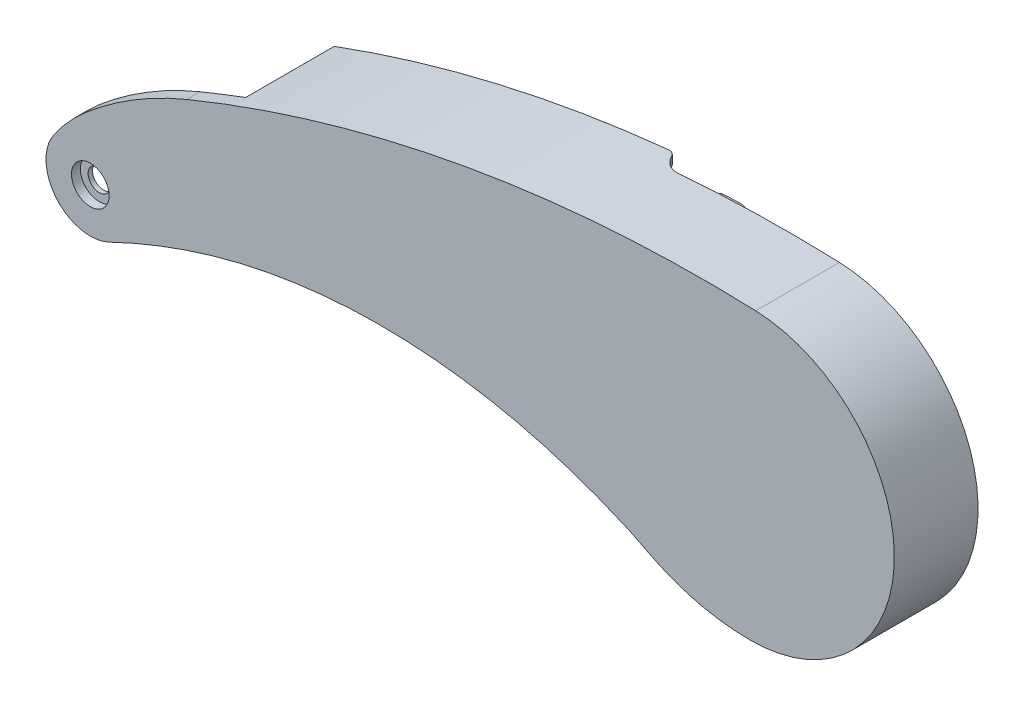
SolidWorks part; units mm, degrees
material "6061-T6 (SS)"
ref_plane "前视基准面" through (0, 0, 0) normal (0, 0, 1) x (1, 0, 0)
ref_plane "上视基准面" through (0, 0, 0) normal (0, 1, 0) x (1, 0, 0)
ref_plane "右视基准面" through (0, 0, 0) normal (1, 0, 0) x (0, 0, -1)
other "Configuration Table"
sketch "草图1" plane through (0, 0, 0) normal (0, 0, 1) x (1, 0, 0)
  line L0 (-74.3846, 0) -> (17.4339, 0) construction
  line L1 (0, 31.8895) -> (0, -25.7876) construction
  line L2 (0, 0) -> (19.2142, 13.9599) construction
  line L3 (0, 0) -> (13.9599, 19.2142) construction
  line L4 (0, 0) -> (-148.9161, -18) construction
  line L6 (0, 0) -> (-1.2281, 22.9672) construction
  line L8 (-1.2281, 22.9672) -> (-150.1441, 4.9672) construction
  line L9 (-150.1441, 4.9672) -> (-148.9161, -18) construction
  line L10 (-148.9161, -18) -> (-97.5528, -158.9319)
  line L12 (0, 0) -> (-103.1063, -167.9797) construction
  circle A117 centre (0, 0) radius 23.75 construction
  circle A118 centre (19.2142, 13.9599) radius 1.6
  circle A119 centre (13.9599, 19.2142) radius 1.6
  circle A120 centre (19.2142, -13.9599) radius 1.6
  circle A121 centre (13.9599, -19.2142) radius 1.6
  circle A122 centre (-13.9599, -19.2142) radius 1.6
  circle A123 centre (-19.2142, -13.9599) radius 1.6
  circle A124 centre (-19.2142, 13.9599) radius 1.6
  circle A125 centre (-13.9599, 19.2142) radius 1.6
  arc A126 (0, -32.5) -> (1.2171, 32.4772) centre (0, 0) ccw
  arc A127 (-157.1671, -12.3502) -> (-144.5702, -27.0063) centre (-148.9161, -18) ccw
  arc A134 (-28.3708, -24.2609) -> (-127.3793, -19.9637) centre (-83.3912, -149.2082) ccw
  arc A135 (-127.3793, -19.9637) -> (-144.5702, -27.0063) centre (-78.0965, -164.7651) ccw
  arc A136 (1.2171, 32.4772) -> (-127.1723, 9.5805) centre (-10.2849, -274.4361) ccw
  arc A138 (-23.6381, -26.5665) -> (-28.3708, -24.2609) centre (-55.9067, -86.7929) ccw
  arc A139 (0, -32.5) -> (-23.6381, -26.5665) centre (0, 17.5518) cw
  circle A153 centre (0, 0) radius 21.8
  arc A155 (-127.1723, 9.5805) -> (-150.1438, -4.5112) centre (-94.9478, -68.7195) ccw
  arc A156 (-150.1438, -4.5112) -> (-157.1671, -12.3502) centre (-123.7132, -35.2574) ccw
  point P27 (0, 0)
  point P73 (0, 0)
  point P83 (0, 0)
  point P105 (0, 0)
  dimension "D3" = 36
  dimension "D4" = 3.2
  dimension "D2" = 47.5
  dimension "D6" = 3.2
  dimension "D8" = 65
  dimension "D15" = 20
  dimension "D16" = 21.8
  dimension "D5" = 18
  dimension "D9" = 18
  dimension "D10" = 150
  dimension "D11" = 23
  dimension "D12" = 150
  dimension "D13" = 103.132
  dimension "D14" = 51.566
  dimension "D7" = 4
extrude "凸台-拉伸1" add sketch "草图1" along normal blind 3 contours A135 A134 A138 A126 A127 A125 A124 A123 A122 A121 A120 A119 A118 region at (-60.0806, 1.6127, 0)
sketch "草图2" plane through (0, 0, 0) normal (0, 0, -1) x (-1, 0, 0)
  line L0 (-28.5, 0) -> (0, 0) construction
  line L2 (0, 0) -> (-20.7479, 9.926) construction
  line L3 (-20.7479, 9.926) -> (128.1682, -8.074) construction
  line L4 (128.1682, -8.074) -> (148.9161, -18) construction
  line L5 (148.9161, -18) -> (265.6411, -112.2087) construction
  line L7 (-13.9568, 11.6234) -> (123.0533, -4.9375) construction
  line L9 (-14.5568, 6.6595) -> (122.4533, -9.9014) construction
  line L11 (19.8643, 25.54) -> (27.8561, 25.1781)
  line L13 (20.7667, -20.0677) -> (28.0595, -16.779)
  line L16 (53.5282, 22.5613) -> (61.4287, 21.3032)
  line L17 (79.2716, 17.6568) -> (87.0322, 15.7143)
  line L19 (80.013, -5.7241) -> (88.0129, -5.7588)
  line L20 (47.3274, -10.2892) -> (55.1237, -8.4956)
  line L21 (0, 0) -> (148.9161, -18) construction
  arc A111 (-1.1422, 30.4786) -> (-30.0624, 5.1483) centre (0, 0) ccw
  arc A112 (0, -30.5) -> (18.2871, -26.8842) centre (0, 17.5518) ccw
  arc A114 (75.0886, -10.9322) -> (61.0732, -12.4928) centre (83.3912, -149.2082) ccw
  arc A116 (144.5702, -27.0063) -> (157.1671, -12.3502) centre (148.9161, -18) ccw
  arc A118 (157.1671, -12.3502) -> (150.1438, -4.5112) centre (123.7132, -35.2574) ccw
  arc A119 (127.1723, 9.5805) -> (-1.2171, 32.4772) centre (10.2849, -274.4361) ccw
  arc A120 (-1.2171, 32.4772) -> (0, -32.5) centre (0, 0) ccw
  arc A121 (-1.0673, 28.48) -> (0, -28.5) centre (0, 0) ccw construction
  arc A122 (0, -32.5) -> (23.6381, -26.5665) centre (0, 17.5518) ccw
  arc A123 (28.3708, -24.2609) -> (23.6381, -26.5665) centre (55.9067, -86.7929) ccw
  arc A124 (127.3793, -19.9637) -> (28.3708, -24.2609) centre (83.3912, -149.2082) ccw
  arc A125 (144.5702, -27.0063) -> (127.3793, -19.9637) centre (78.0965, -164.7651) ccw
  arc A126 (144.5702, -27.0063) -> (157.1671, -12.3502) centre (148.9161, -18) ccw
  arc A128 (127.1723, 9.5805) -> (-1.2171, 32.4772) centre (10.2849, -274.4361) ccw
  arc A129 (-1.2171, 32.4772) -> (0, -32.5) centre (0, 0) ccw
  arc A130 (0, -32.5) -> (23.6381, -26.5665) centre (0, 17.5518) ccw
  arc A131 (28.3708, -24.2609) -> (23.6381, -26.5665) centre (55.9067, -86.7929) ccw
  arc A132 (127.3793, -19.9637) -> (28.3708, -24.2609) centre (83.3912, -149.2082) ccw
  arc A133 (144.5702, -27.0063) -> (127.3793, -19.9637) centre (78.0965, -164.7651) ccw
  arc A134 (0, -28.5) -> (21.749, -23.0407) centre (0, 17.5518) ccw construction
  arc A135 (26.7587, -20.6001) -> (21.749, -23.0407) centre (55.9067, -86.7929) ccw construction
  arc A136 (128.6681, -16.177) -> (26.7587, -20.6001) centre (83.3912, -149.2082) ccw construction
  arc A137 (146.3086, -23.4038) -> (128.6681, -16.177) centre (78.0965, -164.7651) ccw construction
  arc A138 (146.3086, -23.4038) -> (153.7238, -14.4104) centre (148.9161, -18) ccw construction
  arc A139 (153.7238, -14.4104) -> (126.0955, 5.6977) centre (120.8678, -30.5198) ccw construction
  arc A140 (126.0955, 5.6977) -> (-1.0673, 28.48) centre (10.2849, -274.4361) ccw construction
  arc A141 (-28.3421, -2.9958) -> (-28.3421, 2.9958) centre (-28.5, 0) ccw
  arc A142 (-28.3421, 2.9958) -> (-30.0624, 5.1483) centre (-28.2451, 4.837) cw
  arc A143 (-28.3421, -2.9958) -> (-30.0624, -5.1483) centre (-28.2451, -4.837) ccw
  arc A144 (-30.0624, -5.1483) -> (0, -30.5) centre (0, 0) ccw
  circle A145 centre (-28.5, 0) radius 1.6
  arc A146 (-1.1422, 30.4786) -> (0, -30.5) centre (0, 0) ccw construction
  circle A147 centre (-20.7479, 9.926) radius 7 construction
  circle A148 centre (128.1682, -8.074) radius 6 construction
  arc A149 (17.0011, 28.6182) -> (19.8643, 25.54) centre (20, 28.5369) ccw
  arc A150 (27.8561, 25.1781) -> (30.9858, 27.985) centre (27.9918, 28.175) ccw
  arc A151 (17.0011, 28.6182) -> (15.0491, 30.6555) centre (15.0181, 28.672) ccw
  arc A152 (30.9858, 27.985) -> (33.1139, 29.8374) centre (32.9655, 27.8593) cw
  arc A153 (15.0491, 30.6555) -> (-1.1422, 30.4786) centre (10.2849, -274.4361) ccw
  circle A154 centre (20, 28.5369) radius 1.6
  arc A155 (126.6313, 7.6402) -> (-1.1422, 30.4786) centre (10.2849, -274.4361) ccw construction
  arc A156 (19.3156, -24.1418) -> (20.7667, -20.0677) centre (22, -22.8025) cw
  arc A157 (28.0595, -16.779) -> (32.0817, -18.4083) centre (29.2928, -19.5138) cw
  circle A158 centre (22, -22.8025) radius 1.6
  arc A159 (19.3156, -24.1418) -> (18.2871, -26.8842) centre (17.5259, -25.0347) cw
  arc A160 (32.0817, -18.4083) -> (34.6447, -19.5434) centre (33.9409, -17.6713) ccw
  circle A161 centre (54, 25.524) radius 1.6
  arc A162 (27.5648, -22.4305) -> (22.6935, -24.8036) centre (55.9067, -86.7929) ccw construction
  arc A163 (0, -30.5) -> (22.6935, -24.8036) centre (0, 17.5518) ccw construction
  arc A164 (128.0237, -18.0703) -> (27.5648, -22.4305) centre (83.3912, -149.2082) ccw construction
  arc A165 (51.0293, 25.9419) -> (53.5282, 22.5613) centre (54, 25.524) ccw
  arc A166 (61.4287, 21.3032) -> (64.8541, 23.7404) centre (61.9005, 24.2659) ccw
  arc A167 (51.0293, 25.9419) -> (49.3187, 28.1856) centre (49.0649, 26.2183) ccw
  arc A168 (64.8541, 23.7404) -> (67.177, 25.3419) centre (66.8071, 23.393) cw
  arc A169 (49.3187, 28.1856) -> (33.1139, 29.8374) centre (10.2849, -274.4361) ccw
  circle A170 centre (80, 20.567) radius 1.6
  arc A171 (77.077, 21.2425) -> (79.2716, 17.6568) centre (80, 20.567) ccw
  arc A172 (87.0322, 15.7143) -> (90.6571, 17.8435) centre (87.7606, 18.6246) ccw
  arc A173 (77.077, 21.2425) -> (75.5687, 23.6269) centre (75.1443, 21.6892) ccw
  arc A175 (75.5687, 23.6269) -> (67.177, 25.3419) centre (10.2849, -274.4361) ccw
  circle A176 centre (48, -13.2128) radius 1.6
  circle A177 centre (80, -8.7241) radius 1.6
  arc A178 (45.1049, -13.9993) -> (47.3274, -10.2892) centre (48, -13.2128) cw
  arc A180 (45.1049, -13.9993) -> (43.7228, -16.4844) centre (43.1397, -14.5332) cw
  arc A182 (43.7228, -16.4844) -> (34.6447, -19.5434) centre (83.3912, -149.2082) ccw
  arc A183 (77.0018, -8.8285) -> (80.013, -5.7241) centre (80, -8.7241) cw
  arc A184 (88.0129, -5.7588) -> (90.9961, -8.9104) centre (87.9999, -8.7587) cw
  arc A185 (77.0018, -8.8285) -> (75.0886, -10.9322) centre (74.9666, -8.8993) cw
  arc A186 (90.9961, -8.9104) -> (92.8569, -11.0069) centre (92.9935, -9.0116) ccw
  arc A187 (107.3459, -12.77) -> (108.9673, -15.1002) centre (107, -14.7399) cw
  arc A188 (145.4394, -25.205) -> (128.0237, -18.0703) centre (78.0965, -164.7651) ccw construction
  arc A189 (128.0237, -18.0703) -> (27.5648, -22.4305) centre (83.3912, -149.2082) ccw
  arc A190 (145.4394, -25.205) -> (155.4422, -13.3729) centre (148.9161, -18) ccw construction
  arc A191 (75.5687, 23.6269) -> (93.1109, 19.2362) centre (10.2849, -274.4361) cw construction
  arc A192 (90.6571, 17.8435) -> (93.1109, 19.2362) centre (92.5724, 17.327) cw
  arc A193 (155.4422, -13.3729) -> (126.6313, 7.6402) centre (120.8678, -30.5198) ccw construction
  arc A194 (15.0491, 30.6555) -> (33.1139, 29.8374) centre (10.2849, -274.4361) cw construction
  arc A195 (49.3187, 28.1856) -> (67.177, 25.3419) centre (10.2849, -274.4361) cw construction
  arc A196 (93.1109, 19.2362) -> (114.3181, 12.4099) centre (10.2849, -274.4361) cw
  arc A197 (114.3181, 12.4099) -> (116.8779, 13.6021) centre (115, 14.2901) ccw
  arc A198 (55.1237, -8.4956) -> (58.7441, -10.8615) centre (55.7963, -11.4192) cw
  arc A199 (58.7441, -10.8615) -> (61.0732, -12.4928) centre (60.745, -10.4829) ccw
  arc A201 (27.5648, -22.4305) -> (22.6935, -24.8036) centre (55.9067, -86.7929) ccw
  arc A202 (0, -30.5) -> (22.6935, -24.8036) centre (0, 17.5518) ccw
  arc A203 (-1.1422, 30.4786) -> (0, -30.5) centre (0, 0) ccw
  arc A204 (126.4111, 7.731) -> (-1.1422, 30.4786) centre (10.2849, -274.4361) ccw
  arc A205 (148.8401, -6.0279) -> (126.4111, 7.731) centre (94.9478, -68.7195) ccw
  arc A206 (155.5169, -13.4802) -> (148.8401, -6.0279) centre (123.7132, -35.2574) ccw
  arc A207 (157.1671, -12.3502) -> (127.1723, 9.5805) centre (120.8678, -30.5198) ccw construction
  arc A208 (157.1671, -12.3502) -> (150.1438, -4.5112) centre (123.7132, -35.2574) ccw
  arc A209 (150.1438, -4.5112) -> (127.1723, 9.5805) centre (94.9478, -68.7195) ccw
  arc A210 (150.1438, -4.5112) -> (127.1723, 9.5805) centre (94.9478, -68.7195) ccw
  arc A211 (145.4394, -25.205) -> (155.5169, -13.4802) centre (148.9161, -18) ccw
  arc A212 (145.4394, -25.205) -> (128.0237, -18.0703) centre (78.0965, -164.7651) ccw
  point P113 (16.5105, -418.9921)
  arc M20 (127.1723, 9.5805) -> (-1.2171, 32.4772) centre (10.2849, -274.4361) ccw
  arc M21 (-1.2171, 32.4772) -> (0, -32.5) centre (0, 0) ccw
  arc M22 (0, -32.5) -> (23.6381, -26.5665) centre (0, 17.5518) ccw
  arc M23 (23.6381, -26.5665) -> (28.3708, -24.2609) centre (55.9067, -86.7929) cw
  arc M24 (28.3708, -24.2609) -> (127.3793, -19.9637) centre (83.3912, -149.2082) cw
  arc M25 (127.3793, -19.9637) -> (144.5702, -27.0063) centre (78.0965, -164.7651) cw
  dimension "D7" = 150
  dimension "D9" = 14
  dimension "D11" = 12
  dimension "D12" = 150
  dimension "D13" = 8
  dimension "D10" = 2.5
  dimension "D8" = 166.66
  dimension "D14" = 20
  dimension "D15" = 8
  dimension "D16" = 8
  dimension "D17" = 8
  dimension "D18" = 54
  dimension "D19" = 80
  dimension "D20" = 8
  dimension "D21" = 48
  dimension "D22" = 80
  dimension "D23" = 8
  dimension "D6" = 23
  dimension "D25" = 107
  dimension "D26" = 2
  dimension "D27" = 115
  dimension "D28" = 22
  dimension "D4" = 6
  dimension "D5" = 3.2
  dimension "D24" = 2
  dimension "D29" = 2
  dimension "D30" = 2
  dimension "D1" = 0
  dimension "D2" = 2
  dimension "D3" = 2
extrude "凸台-拉伸2" add sketch "草图2" along normal blind 20 contours M20 M21 M22 M23 M24 M25 | A152 A204 A151 A149 L11 A150 A154 | A168 A204 A167 A165 L16 A166 A161 | A192 A204 A173 A171 L17 A172 A170 | A189 A186 A184 L19 A183 A185 A177 | A199 A198 L20 A178 A180 A189 A176 | A159 A202 A201 A189 A160 A157 L13 A156 A158 | A142 A203 A143 A141 A145 region at (-24.5149, 27.9422, 0) region at (-6.9345, 32.3042, 0) region at (-58.4194, 24.4254, 0) region at (29.7748, 3.6145, 0) region at (-84.3067, 19.0872, 0) region at (-25.9289, -20.6304, 0) region at (-52.3362, -11.8146, 0) region at (-84.5374, -8.3524, 0)
sketch "草图4" plane through (0, 0, -20) normal (0, 0, -1) x (-1, 0, 0)
  line L0 (20, 28.5369) -> (27.9918, 28.175) construction
  line L3 (61.9005, 24.2659) -> (54, 25.524) construction
  line L8 (80, 20.567) -> (87.7606, 18.6246) construction
  line L9 (22, -22.8025) -> (29.2928, -19.5138) construction
  line L10 (48, -13.2128) -> (55.7963, -11.4192) construction
  line L11 (80, -8.7241) -> (87.9999, -8.7587) construction
  line L12 (29.2928, -19.5138) -> (25.6464, -21.1581) construction
  line L15 (29.9094, -20.8812) -> (26.263, -22.5255)
  line L24 (28.6761, -18.1464) -> (25.0297, -19.7907)
  line L27 (27.9918, 28.175) -> (23.9959, 28.356) construction
  line L30 (27.924, 26.6766) -> (23.9281, 26.8575)
  line L33 (28.0597, 29.6735) -> (24.0638, 29.8545)
  line L36 (61.9005, 24.2659) -> (57.9502, 24.8949) construction
  line L39 (87.7606, 18.6246) -> (83.8803, 19.5958) construction
  line L40 (87.3964, 17.1695) -> (83.5161, 18.1407)
  line L41 (88.1248, 20.0797) -> (84.2445, 21.0509)
  line L42 (87.9999, -8.7587) -> (84, -8.7414) construction
  line L43 (87.9934, -10.2587) -> (83.9935, -10.2414)
  line L44 (88.0064, -7.2587) -> (84.0065, -7.2414)
  line L45 (55.7963, -11.4192) -> (51.8982, -12.316) construction
  line L46 (56.1326, -12.881) -> (52.2345, -13.7778)
  line L47 (55.46, -9.9574) -> (51.5619, -10.8542)
  line L48 (61.6646, 22.7845) -> (57.7143, 23.4136)
  line L49 (62.1363, 25.7472) -> (58.1861, 26.3763)
  arc A24 (29.9094, -20.8812) -> (28.6761, -18.1464) centre (29.2928, -19.5138) ccw
  arc A25 (25.0297, -19.7907) -> (26.263, -22.5255) centre (25.6464, -21.1581) ccw
  arc A26 (27.924, 26.6766) -> (28.0597, 29.6735) centre (27.9918, 28.175) ccw
  arc A27 (24.0638, 29.8545) -> (23.9281, 26.8575) centre (23.9959, 28.356) ccw
  arc A30 (87.3964, 17.1695) -> (88.1248, 20.0797) centre (87.7606, 18.6246) ccw
  arc A31 (84.2445, 21.0509) -> (83.5161, 18.1407) centre (83.8803, 19.5958) ccw
  arc A32 (87.9934, -10.2587) -> (88.0064, -7.2587) centre (87.9999, -8.7587) ccw
  arc A33 (84.0065, -7.2414) -> (83.9935, -10.2414) centre (84, -8.7414) ccw
  arc A34 (56.1326, -12.881) -> (55.46, -9.9574) centre (55.7963, -11.4192) ccw
  arc A35 (51.5619, -10.8542) -> (52.2345, -13.7778) centre (51.8982, -12.316) ccw
  arc A36 (61.6646, 22.7845) -> (62.1363, 25.7472) centre (61.9005, 24.2659) ccw
  arc A37 (58.1861, 26.3763) -> (57.7143, 23.4136) centre (57.9502, 24.8949) ccw
  point P12 (27.4696, -20.3359)
  point P18 (25.9939, 28.2655)
  point P24 (59.9253, 24.5804)
  point P30 (85.8204, 19.1102)
  point P36 (85.9999, -8.7501)
  point P42 (53.8473, -11.8676)
  dimension "D2" = 1.5
  dimension "D1" = 4
extrude "凸台-拉伸3" add sketch "草图4" along normal blind 3 contours L44 A33 L43 A32 | L33 A27 L30 A26 | L49 A37 L48 A36 | A30 L41 A31 L40 | A34 L47 A35 L46 | A24 L24 A25 L15 region at (-85.9999, -8.7501, -20)
sketch "草图5" plane through (0, 0, -20) normal (0, 0, -1) x (-1, 0, 0)
  circle A0 centre (80, -8.7241) radius 1.6 construction
  circle A2 centre (-28.5, 0) radius 1.6 construction
  circle A4 centre (-28.5, 0) radius 1.6
  circle A6 centre (54, 25.524) radius 1.6 construction
  circle A8 centre (80, 20.567) radius 1.6 construction
  circle A10 centre (80, -8.7241) radius 1.6
  circle A12 centre (48, -13.2128) radius 1.6 construction
  circle A14 centre (22, -22.8025) radius 1.6 construction
  circle A27 centre (20, 28.5369) radius 1.6 construction
  circle A28 centre (54, 25.524) radius 1.6
  circle A29 centre (80, 20.567) radius 1.6
  circle A31 centre (48, -13.2128) radius 1.6
  circle A32 centre (22, -22.8025) radius 1.6
  circle A33 centre (20, 28.5369) radius 1.6
extrude "切除-拉伸1" cut sketch "草图5" against normal up to next
sketch "草图10" plane through (0, 0, 0) normal (0, 0, -1) x (-1, 0, 0)
  circle A0 centre (148.9161, -18) radius 2.5
  dimension "D1" = 5
extrude "切除-拉伸4" cut sketch "草图10" against normal up to next
sketch "草图11" plane through (0, 0, 3) normal (0, 0, 1) x (1, 0, 0)
  circle A0 centre (-148.9161, -18) radius 4.25
  dimension "D1" = 8.5
extrude "切除-拉伸5" cut sketch "草图11" against normal blind 2
sketch "草图13" plane through (0, 0, 3) normal (0, 0, 1) x (1, 0, 0)
  line L0 (-82.9126, 19.8482) -> (-83.8746, 23.7461)
  line L1 (-77.0737, 21.2281) -> (-77.9584, 25.1442)
  line L2 (-56.9642, 25.062) -> (-57.5825, 29.0289)
  line L3 (-51.0272, 25.9272) -> (-51.5669, 29.9056)
  line L4 (-22.9974, 28.4111) -> (-23.1657, 32.4224)
  line L5 (-17.0007, 28.6034) -> (-17.0897, 32.6173)
  line L6 (-83, -8.7157) -> (-83.011, -12.6837)
  line L7 (-77.0031, -8.8605) -> (-77.1835, -12.8243)
  line L10 (-24.5347, -21.1976) -> (-26.898, -24.9303)
  line L11 (-19.2779, -24.0635) -> (-21.0383, -27.8637)
  line L12 (28.5, 3) -> (32.3612, 3)
  line L13 (28.5, -3) -> (32.3612, -3)
  line L14 (28.5, 3) -> (28.5, -3) construction
  line L16 (-45.1135, -14.0301) -> (-46.1946, -17.848)
  line L17 (-50.9188, -12.5194) -> (-51.8359, -16.3799)
  arc A0 (-82.9126, 19.8482) -> (-77.0737, 21.2281) centre (-80, 20.567) ccw
  arc A1 (-56.9642, 25.062) -> (-51.0272, 25.9272) centre (-54, 25.524) ccw
  arc A2 (-22.9974, 28.4111) -> (-17.0007, 28.6034) centre (-20, 28.5369) ccw
  arc A3 (28.5, 3) -> (28.5, -3) centre (28.5, 0) ccw
  arc A5 (-45.1135, -14.0301) -> (-50.9676, -12.7729) centre (-48, -13.2128) ccw
  arc A7 (-23.6381, -26.5665) -> (0, -32.5) centre (0, 17.5518) ccw construction
  arc A8 (1.2171, 32.4772) -> (-127.1723, 9.5805) centre (-10.2849, -274.4361) ccw construction
  arc A9 (-28.3708, -24.2609) -> (-127.3793, -19.9637) centre (-83.3912, -149.2082) ccw construction
  arc A11 (-23.6381, -26.5665) -> (-28.3708, -24.2609) centre (-55.9067, -86.7929) ccw construction
  arc A12 (0, -32.5) -> (1.2171, 32.4772) centre (0, 0) ccw construction
  arc A13 (-17.0897, 32.6173) -> (-23.1657, 32.4224) centre (-10.2849, -274.4361) ccw
  arc A15 (32.3612, -3) -> (32.3612, 3) centre (0, 0) ccw
  arc A16 (-77.1835, -12.8243) -> (-83.011, -12.6837) centre (-83.3912, -149.2082) ccw
  arc A18 (-19.2779, -24.0635) -> (-24.5347, -21.1976) centre (-22, -22.8025) ccw
  arc A19 (-46.1946, -17.848) -> (-51.8359, -16.3799) centre (-83.3912, -149.2082) ccw
  arc A20 (-77.0031, -8.8605) -> (-83, -8.7157) centre (-80, -8.7241) ccw
  arc A21 (-77.9584, 25.1442) -> (-83.8746, 23.7461) centre (-10.2849, -274.4361) ccw
  arc A22 (-51.5669, 29.9056) -> (-57.5825, 29.0289) centre (-10.2849, -274.4361) ccw
  arc A23 (-23.6381, -26.5665) -> (-21.0383, -27.8637) centre (0, 17.5518) ccw
  arc A24 (-23.6381, -26.5665) -> (-26.898, -24.9303) centre (-55.9067, -86.7929) ccw
  circle M9 centre (28.5, 0) radius 1.6
  circle M10 centre (-54, 25.524) radius 1.6
  circle M11 centre (-80, 20.567) radius 1.6
  circle M12 centre (-80, -8.7241) radius 1.6
  circle M13 centre (-48, -13.2128) radius 1.6
  circle M14 centre (-22, -22.8025) radius 1.6
  circle M15 centre (-20, 28.5369) radius 1.6
  arc M17 (-127.3793, -19.9637) -> (-28.3708, -24.2609) centre (-83.3912, -149.2082) cw
  arc M19 (-23.6381, -26.5665) -> (0, -32.5) centre (0, 17.5518) ccw
  arc M20 (0, -32.5) -> (1.2171, 32.4772) centre (0, 0) ccw
  arc M21 (1.2171, 32.4772) -> (-127.1723, 9.5805) centre (-10.2849, -274.4361) ccw
  dimension "D1" = 6
  dimension "D2" = 6
  dimension "D3" = 3
  dimension "D4" = 6
  dimension "D5" = 0
extrude "切除-拉伸6" cut sketch "草图13" against normal blind 2 contours A5 M17 M13 | L11 A18 L10 M19 M14 | L12 L14 L13 M9 M20 | L14 A3 M9 | L4 A2 L5 M21 M15 | L2 A1 L3 M21 M10 | L0 A0 L1 M21 M11 | L7 A20 L6 M17 M12 region at (-22.2972, -27.133, 3) region at (30.7421, 0, 3) region at (-20.1252, 32.441, 3) region at (-54.5626, 29.3843, 3) region at (-83.2943, 21.8217, 3) region at (28.4329, 2.3, 3) region at (-79.9298, -5.8179, 3) region at (-51.2776, -14.4733, 3)
sketch "草图14" plane through (0, 0, 0) normal (0, 0, -1) x (-1, 0, 0)
  circle A0 centre (148.9161, -18) radius 10
  circle A1 centre (148.9161, -18) radius 7
  dimension "D1" = 14
  dimension "D2" = 20
extrude "凸台-拉伸4" add sketch "草图14" along normal blind 1.5
sketch "草图16" plane through (0, 0, 0) normal (0, 0, -1) x (-1, 0, 0)
  line L2 (69.9, 24.8123) -> (66.5383, -11.7121)
  line L3 (72.857, 24.208) -> (69.5822, -11.3731)
  line L4 (41.2273, 29.1197) -> (39.1573, -17.9354) construction
  line L5 (68.061, -11.534) -> (71.3789, 24.5139) construction
  line L6 (39.7324, 29.2684) -> (37.6328, -18.459)
  line L7 (42.7219, 28.9636) -> (40.6809, -17.4318)
  line L8 (103.7768, 16.0167) -> (100.1246, -11.6975) construction
  line L9 (102.3249, 16.48) -> (98.6344, -11.5244)
  line L10 (105.2277, 15.5457) -> (101.6126, -11.8868)
  arc A0 (69.5822, -11.3731) -> (66.5383, -11.7121) centre (83.3912, -149.2082) ccw
  arc A1 (72.857, 24.208) -> (69.9, 24.8123) centre (10.2849, -274.4361) ccw
  arc A2 (43.7228, -16.4844) -> (34.6447, -19.5434) centre (83.3912, -149.2082) ccw construction
  arc A5 (49.3187, 28.1856) -> (33.1139, 29.8374) centre (10.2849, -274.4361) ccw construction
  arc A8 (75.5687, 23.6269) -> (67.177, 25.3419) centre (10.2849, -274.4361) ccw construction
  arc A9 (75.0886, -10.9322) -> (61.0732, -12.4928) centre (83.3912, -149.2082) ccw construction
  arc A10 (75.0886, -10.9322) -> (61.0732, -12.4928) centre (83.3912, -149.2082) ccw construction
  arc A11 (49.3187, 28.1856) -> (33.1139, 29.8374) centre (10.2849, -274.4361) ccw construction
  arc A12 (43.7228, -16.4844) -> (34.6447, -19.5434) centre (83.3912, -149.2082) ccw construction
  arc A13 (40.6809, -17.4318) -> (37.6328, -18.459) centre (83.3912, -149.2082) ccw
  arc A14 (42.7219, 28.9636) -> (39.7324, 29.2684) centre (10.2849, -274.4361) ccw
  arc A15 (114.3181, 12.4099) -> (93.1109, 19.2362) centre (10.2849, -274.4361) ccw construction
  arc A16 (107.3459, -12.77) -> (92.8569, -11.0069) centre (83.3912, -149.2082) ccw construction
  arc A17 (101.6126, -11.8868) -> (98.6344, -11.5244) centre (83.3912, -149.2082) ccw
  arc A18 (105.2277, 15.5457) -> (102.3249, 16.48) centre (10.2849, -274.4361) ccw
  point P33 (71.3789, 24.5139)
  dimension "D3" = 3
  dimension "D1" = 3
  dimension "D2" = 3
extrude "凸台-拉伸5" add sketch "草图16" along normal blind 2
sketch "草图17" plane through (0, 0, 0) normal (0, 0, -1) x (-1, 0, 0)
  line L0 (41.7014, 5.7659) -> (100.4797, 2.4778) construction
  line L1 (40.6809, -17.4318) -> (42.7219, 28.9636) construction
  line L2 (102.3249, 16.48) -> (98.6344, -11.5244) construction
  line L3 (41.7673, 7.2646) -> (100.6762, 3.9692)
  line L4 (102.3249, 16.48) -> (98.6344, -11.5244) construction
  line L5 (41.6355, 4.2673) -> (100.2831, 0.9865)
  line L6 (100.6762, 3.9692) -> (100.2831, 0.9865)
  line L7 (41.6355, 4.2673) -> (41.7673, 7.2646)
  dimension "D1" = 3
extrude "凸台-拉伸6" add sketch "草图17" along normal blind 2
fillet "圆角1" radius 2 14 edges at (-83.8746, 23.7461, 2) (-77.9584, 25.1442, 2) (-57.5825, 29.0289, 2) (-51.5669, 29.9056, 2) (-77.1835, -12.8243, 2) (-83.011, -12.6837, 2) (-21.0383, -27.8637, 2) (32.3612, 3, 2) (32.3612, -3, 2) (-23.1657, 32.4224, 2) (-17.0897, 32.6173, 2) (-46.1946, -17.848, 2) (-51.8359, -16.3799, 2) (-26.898, -24.9303, 2)
sketch "草图20" plane through (0, 0, 3) normal (0, 0, 1) x (1, 0, 0)
  line L0 (30.0874, 3) -> (28.5, 3) construction
  line L1 (28.5, -3) -> (30.0874, -3) construction
  line L2 (-20.1802, -26.0112) -> (-19.2779, -24.0635) construction
  line L3 (-24.5347, -21.1976) -> (-25.967, -23.4599) construction
  line L4 (-45.6536, -15.9376) -> (-45.1135, -14.0301) construction
  line L5 (-50.9188, -12.5194) -> (-51.377, -14.4481) construction
  line L6 (-77.0932, -10.8408) -> (-77.0031, -8.8605) construction
  line L7 (-83, -8.7157) -> (-83.0055, -10.6981) construction
  line L8 (-23.0816, 30.4176) -> (-22.9974, 28.4111) construction
  line L9 (-17.0007, 28.6034) -> (-17.0452, 30.6112) construction
  line L10 (-57.2735, 27.0463) -> (-56.9642, 25.062) construction
  line L11 (-51.0272, 25.9272) -> (-51.2972, 27.9173) construction
  line L12 (-83.3938, 21.798) -> (-82.9126, 19.8482) construction
  line L13 (-77.0737, 21.2281) -> (-77.5162, 23.187) construction
  line L14 (30.0874, 3) -> (28.5, 3)
  line L15 (28.5, -3) -> (30.0874, -3)
  line L16 (-20.1802, -26.0112) -> (-19.2779, -24.0635)
  line L17 (-24.5347, -21.1976) -> (-25.967, -23.4599)
  line L18 (-45.6536, -15.9376) -> (-45.1135, -14.0301)
  line L19 (-50.9188, -12.5194) -> (-51.377, -14.4481)
  line L20 (-77.0932, -10.8408) -> (-77.0031, -8.8605)
  line L21 (-83, -8.7157) -> (-83.0055, -10.6981)
  line L22 (-23.0816, 30.4176) -> (-22.9974, 28.4111)
  line L23 (-17.0007, 28.6034) -> (-17.0452, 30.6112)
  line L24 (-57.2735, 27.0463) -> (-56.9642, 25.062)
  line L25 (-51.0272, 25.9272) -> (-51.2972, 27.9173)
  line L26 (-83.3938, 21.798) -> (-82.9126, 19.8482)
  line L27 (-77.0737, 21.2281) -> (-77.5162, 23.187)
  arc A0 (28.5, 3) -> (28.5, -3) centre (28.5, 0) ccw construction
  arc A1 (32.0603, -5.3279) -> (30.0874, -3) centre (30.0874, -5) ccw construction
  arc A2 (32.0603, -5.3279) -> (32.0603, 5.3279) centre (0, 0) ccw construction
  arc A3 (30.0874, 3) -> (32.0603, 5.3279) centre (30.0874, 5) ccw construction
  arc A4 (-19.2779, -24.0635) -> (-24.5347, -21.1976) centre (-22, -22.8025) ccw construction
  arc A5 (-28.4615, -24.221) -> (-25.967, -23.4599) centre (-27.6568, -22.39) ccw construction
  arc A7 (-23.6381, -26.5665) -> (-19.1298, -28.7) centre (0, 17.5518) ccw construction
  arc A8 (-20.1802, -26.0112) -> (-19.1298, -28.7) centre (-18.3654, -26.8519) ccw construction
  arc A9 (-45.1135, -14.0301) -> (-50.9188, -12.5194) centre (-48, -13.2128) ccw construction
  arc A10 (-53.7569, -15.9382) -> (-51.377, -14.4481) centre (-53.3228, -13.9859) ccw construction
  arc A11 (-44.3019, -18.3987) -> (-53.7569, -15.9382) centre (-83.3912, -149.2082) ccw construction
  arc A12 (-45.6536, -15.9376) -> (-44.3019, -18.3987) centre (-43.7293, -16.4825) ccw construction
  arc A13 (-77.0031, -8.8605) -> (-83, -8.7157) centre (-80, -8.7241) ccw construction
  arc A14 (-84.9822, -12.6924) -> (-83.0055, -10.6981) centre (-85.0055, -10.6925) ccw construction
  arc A15 (-75.2151, -12.9282) -> (-84.9822, -12.6924) centre (-83.3912, -149.2082) ccw construction
  arc A16 (-77.0932, -10.8408) -> (-75.2151, -12.9282) centre (-75.0953, -10.9318) ccw construction
  arc A17 (-22.9974, 28.4111) -> (-17.0007, 28.6034) centre (-20, 28.5369) ccw construction
  arc A18 (-15.0769, 32.6553) -> (-17.0452, 30.6112) centre (-15.0457, 30.6555) ccw construction
  arc A19 (-15.0769, 32.6553) -> (-25.1768, 32.3314) centre (-10.2849, -274.4361) ccw construction
  arc A20 (-23.0816, 30.4176) -> (-25.1768, 32.3314) centre (-25.0798, 30.3338) ccw construction
  arc A21 (-56.9642, 25.062) -> (-51.0272, 25.9272) centre (-54, 25.524) ccw construction
  arc A22 (-49.5711, 30.1696) -> (-51.2972, 27.9173) centre (-49.3153, 28.1861) ccw construction
  arc A23 (-49.5711, 30.1696) -> (-59.5706, 28.7124) centre (-10.2849, -274.4361) ccw construction
  arc A24 (-57.2735, 27.0463) -> (-59.5706, 28.7124) centre (-59.2496, 26.7383) ccw construction
  arc A25 (-82.9126, 19.8482) -> (-77.0737, 21.2281) centre (-80, 20.567) ccw construction
  arc A26 (-75.9933, 25.5814) -> (-77.5162, 23.187) centre (-75.5654, 23.6277) ccw construction
  arc A27 (-75.9933, 25.5814) -> (-85.8275, 23.2574) centre (-10.2849, -274.4361) ccw construction
  arc A28 (-83.3938, 21.798) -> (-85.8275, 23.2574) centre (-85.3355, 21.3188) ccw construction
  arc A29 (28.5, 3) -> (28.5, -3) centre (28.5, 0) ccw
  arc A30 (32.0603, -5.3279) -> (30.0874, -3) centre (30.0874, -5) ccw
  arc A31 (32.0603, -5.3279) -> (32.0603, 5.3279) centre (0, 0) ccw
  arc A32 (30.0874, 3) -> (32.0603, 5.3279) centre (30.0874, 5) ccw
  arc A33 (-19.2779, -24.0635) -> (-24.5347, -21.1976) centre (-22, -22.8025) ccw
  arc A34 (-28.4615, -24.221) -> (-25.967, -23.4599) centre (-27.6568, -22.39) ccw
  arc A35 (-23.6381, -26.5665) -> (-28.4615, -24.221) centre (-55.9071, -86.7927) ccw
  arc A36 (-23.6381, -26.5665) -> (-19.1298, -28.7) centre (0, 17.5518) ccw
  arc A37 (-20.1802, -26.0112) -> (-19.1298, -28.7) centre (-18.3654, -26.8519) ccw
  arc A38 (-45.1135, -14.0301) -> (-50.9188, -12.5194) centre (-48, -13.2128) ccw
  arc A39 (-53.7569, -15.9382) -> (-51.377, -14.4481) centre (-53.3228, -13.9859) ccw
  arc A40 (-44.3019, -18.3987) -> (-53.7569, -15.9382) centre (-83.3912, -149.2082) ccw
  arc A41 (-45.6536, -15.9376) -> (-44.3019, -18.3987) centre (-43.7293, -16.4825) ccw
  arc A42 (-77.0031, -8.8605) -> (-83, -8.7157) centre (-80, -8.7241) ccw
  arc A43 (-84.9822, -12.6924) -> (-83.0055, -10.6981) centre (-85.0055, -10.6925) ccw
  arc A44 (-75.2151, -12.9282) -> (-84.9822, -12.6924) centre (-83.3912, -149.2082) ccw
  arc A45 (-77.0932, -10.8408) -> (-75.2151, -12.9282) centre (-75.0953, -10.9318) ccw
  arc A46 (-22.9974, 28.4111) -> (-17.0007, 28.6034) centre (-20, 28.5369) ccw
  arc A47 (-15.0769, 32.6553) -> (-17.0452, 30.6112) centre (-15.0457, 30.6555) ccw
  arc A48 (-15.0769, 32.6553) -> (-25.1768, 32.3314) centre (-10.2849, -274.4361) ccw
  arc A49 (-23.0816, 30.4176) -> (-25.1768, 32.3314) centre (-25.0798, 30.3338) ccw
  arc A50 (-56.9642, 25.062) -> (-51.0272, 25.9272) centre (-54, 25.524) ccw
  arc A51 (-49.5711, 30.1696) -> (-51.2972, 27.9173) centre (-49.3153, 28.1861) ccw
  arc A52 (-49.5711, 30.1696) -> (-59.5706, 28.7124) centre (-10.2849, -274.4361) ccw
  arc A53 (-57.2735, 27.0463) -> (-59.5706, 28.7124) centre (-59.2496, 26.7383) ccw
  arc A54 (-82.9126, 19.8482) -> (-77.0737, 21.2281) centre (-80, 20.567) ccw
  arc A55 (-75.9933, 25.5814) -> (-77.5162, 23.187) centre (-75.5654, 23.6277) ccw
  arc A56 (-75.9933, 25.5814) -> (-85.8275, 23.2574) centre (-10.2849, -274.4361) ccw
  arc A57 (-83.3938, 21.798) -> (-85.8275, 23.2574) centre (-85.3355, 21.3188) ccw
  circle A58 centre (-19.2142, -13.9599) radius 1.6 construction
  circle A59 centre (-13.9599, -19.2142) radius 1.6 construction
  circle A60 centre (13.9599, -19.2142) radius 1.6 construction
  circle A61 centre (19.2142, -13.9599) radius 1.6 construction
  circle A62 centre (19.2142, 13.9599) radius 1.6 construction
  circle A63 centre (13.9599, 19.2142) radius 1.6 construction
  circle A64 centre (0, 0) radius 21.8 construction
  circle A65 centre (-19.2142, 13.9599) radius 1.6 construction
  circle A66 centre (-13.9599, 19.2142) radius 1.6 construction
  circle A67 centre (-19.2142, -13.9599) radius 1.6
  circle A68 centre (-13.9599, -19.2142) radius 1.6
  circle A69 centre (13.9599, -19.2142) radius 1.6
  circle A70 centre (19.2142, -13.9599) radius 1.6
  circle A71 centre (19.2142, 13.9599) radius 1.6
  circle A72 centre (13.9599, 19.2142) radius 1.6
  circle A73 centre (0, 0) radius 21.8
  circle A74 centre (-19.2142, 13.9599) radius 1.6
  circle A75 centre (-13.9599, 19.2142) radius 1.6
extrude "凸台-拉伸7" add sketch "草图20" against normal up to surface (3 mm away) up to face at (20.8142, 13.9599, 0)
sketch "草图21" plane through (0, 0, -20) normal (0, 0, -1) x (-1, 0, 0)
  circle A0 centre (-28.5, 0) radius 1.6 construction
  circle A1 centre (22, -22.8025) radius 1.6 construction
  circle A2 centre (48, -13.2128) radius 1.6 construction
  circle A3 centre (80, -8.7241) radius 1.6 construction
  circle A4 centre (80, 20.567) radius 1.6 construction
  circle A5 centre (54, 25.524) radius 1.6 construction
  circle A6 centre (20, 28.5369) radius 1.6 construction
  circle A7 centre (-28.5, 0) radius 1.6
  circle A8 centre (22, -22.8025) radius 1.6
  circle A9 centre (48, -13.2128) radius 1.6
  circle A10 centre (80, -8.7241) radius 1.6
  circle A11 centre (80, 20.567) radius 1.6
  circle A12 centre (54, 25.524) radius 1.6
  circle A13 centre (20, 28.5369) radius 1.6
extrude "凸台-拉伸8" add sketch "草图21" against normal up to surface (20 mm away) up to face at (-18.4, 28.5369, 0)
sketch "草图25" plane through (0, 0, 0) normal (0, 0, -1) x (-1, 0, 0)
  line L0 (38.7718, 7.4321) -> (6.0287, 9.2638)
  line L1 (39.7324, 29.2684) -> (37.6328, -18.459) construction
  line L2 (38.64, 4.4348) -> (5.6894, 6.2781)
  line L3 (68.1491, 5.7888) -> (41.7673, 7.2646) construction
  line L4 (41.6355, 4.2673) -> (67.8739, 2.7995) construction
  line L5 (38.7718, 7.4321) -> (38.64, 4.4348)
  line L6 (8.4634, 30.6872) -> (6.0287, 9.2638)
  line L7 (5.4403, 30.6542) -> (3.0284, 9.4317)
  line L8 (6.9523, 30.6745) -> (0, -30.5) construction
  line L9 (5.6894, 6.2781) -> (3.2186, -15.4623)
  line L10 (3.0284, 9.4317) -> (-28.3738, 11.1883)
  line L11 (2.6891, 6.4459) -> (0.2378, -15.1236)
  line L12 (2.6891, 6.4459) -> (-29.3661, 8.2391)
  line L13 (-28.0805, -11.9053) -> (0.2378, -15.1236)
  line L14 (-26.4972, -15.1045) -> (-0.1009, -18.1044)
  line L15 (3.2186, -15.4623) -> (25.3914, -17.9822)
  line L16 (20.7667, -20.0677) -> (28.0595, -16.779) construction
  line L17 (2.8799, -18.4432) -> (20.0437, -20.3938)
  line L18 (20.7667, -20.0677) -> (28.0595, -16.779) construction
  line L19 (20.0437, -20.3938) -> (25.3914, -17.9822)
  line L20 (2.8799, -18.4432) -> (1.5124, -30.4762)
  line L21 (-0.1009, -18.1044) -> (-1.5054, -30.4628)
  arc A0 (-1.1422, 30.4786) -> (-30.0624, 5.1483) centre (0, 0) ccw construction
  arc A1 (-28.3738, 11.1883) -> (-29.3661, 8.2391) centre (0, 0) ccw
  arc A2 (15.0491, 30.6555) -> (-1.1422, 30.4786) centre (10.2849, -274.4361) ccw construction
  arc A3 (-30.0624, -5.1483) -> (0, -30.5) centre (0, 0) ccw construction
  arc A4 (15.0491, 30.6555) -> (-1.1422, 30.4786) centre (10.2849, -274.4361) ccw construction
  arc A5 (-30.0624, -5.1483) -> (0, -30.5) centre (0, 0) ccw construction
  arc A6 (8.4634, 30.6872) -> (5.4403, 30.6542) centre (10.2849, -274.4361) ccw
  arc A8 (-28.0805, -11.9053) -> (-26.4972, -15.1045) centre (0, 0) ccw
  arc A9 (-1.5054, -30.4628) -> (0, -30.5) centre (0, 0) ccw
  arc A10 (0, -30.5) -> (18.2871, -26.8842) centre (0, 17.5518) ccw construction
  arc A11 (0, -30.5) -> (1.5124, -30.4762) centre (0, 17.5518) ccw
  dimension "D4" = 30.5
  dimension "D1" = 3
  dimension "D2" = 3
  dimension "D3" = 15
extrude "凸台-拉伸9" add sketch "草图25" along normal blind 2
sketch "草图26" plane through (0, 0, 0) normal (0, 1, 0) x (1, 0, 0)
  line L0 (0, 20) -> (-41.41, 20) construction
  line L1 (32.5, 15.9) -> (-35, 15.9)
  line L2 (32.5, -3) -> (32.5, 20) construction
  line L3 (32.5, 20) -> (0, 20) construction
  line L4 (1.2171, 20) -> (-116.8779, 20) construction
  line L5 (-41.41, 20) -> (-32.2761, 20) construction
  line L6 (32.5, 15.9) -> (36.9453, 15.9)
  line L7 (36.9453, 15.9) -> (36.9453, 30.4956)
  line L8 (36.9453, 30.4956) -> (-41.41, 30.4956)
  line L9 (-41.41, 30.4956) -> (-41.41, 20)
  line L10 (-39.7153, 19.035) -> (-39.2785, 18.3127)
  arc A1 (-39.7153, 19.035) -> (-41.41, 20) centre (-41.4267, 18.0001) ccw
  arc A2 (-39.2785, 18.3127) -> (-35, 15.9) centre (-35, 20.9) ccw
  dimension "D2" = 2
  dimension "D3" = 5
  dimension "D1" = 35
  dimension "D4" = 4.1
  dimension "D5" = 6.41
extrude "切除-拉伸7" cut sketch "草图26" against normal through all both and the other way through all
sketch "草图31" plane through (0, 0, -20) normal (0, 0, -1) x (-1, 0, 0)
  point P0 (54, 25.524)
  point P1 (48, -13.2128)
  point P3 (80, -8.7241)
  point P5 (80, 20.567)
hole_wizard "M3 螺纹孔4" positions "草图31" profile "草图32" tap size "M3" standard "GB"
sketch "草图32" plane through (-54, 25.524, -20) normal (1, 0, 0) x (0, 1, 0)
  line L0 (0, 0) -> (0, 5.7511)
  line L1 (0, 5.7511) -> (1.25, 5)
  line L2 (1.25, 5) -> (1.25, 0)
  line L5 (1.25, 0) -> (0, 0)
  line L10 (0, 5.7511) -> (-1.25, 5) construction
  line L11 (0, -6.35) -> (0, 107.95) construction
  dimension "螺纹孔钻头直径" = 2.5
  dimension "螺纹孔钻头深度" = 5
  dimension "导头角度" = 118
cosmetic thread "孔螺蚊线15" parameters "D1"=6, "D2"=3
cosmetic thread "孔螺蚊线16" parameters "D1"=6, "D2"=3
cosmetic thread "孔螺蚊线17" parameters "D1"=6, "D2"=3
cosmetic thread "孔螺蚊线18" parameters "D1"=6, "D2"=3
sketch "草图33" plane through (0, 0, -15.9) normal (0, 0, -1) x (-1, 0, 0)
  point P0 (20, 28.5369)
  point P1 (22, -22.8025)
  point P3 (-28.5, 0)
hole_wizard "M3 螺纹孔5" positions "草图33" profile "草图34" tap size "M3" standard "GB"
sketch "草图34" plane through (-20, 28.5369, -15.9) normal (1, 0, 0) x (0, 1, 0)
  line L0 (0, 0) -> (0, 5.7511)
  line L1 (0, 5.7511) -> (1.25, 5)
  line L2 (1.25, 5) -> (1.25, 0)
  line L5 (1.25, 0) -> (0, 0)
  line L10 (0, 5.7511) -> (-1.25, 5) construction
  line L11 (0, -6.35) -> (0, 107.95) construction
  dimension "螺纹孔钻头直径" = 2.5
  dimension "螺纹孔钻头深度" = 5
  dimension "导头角度" = 118
cosmetic thread "孔螺蚊线19" parameters "D1"=6, "D2"=3
cosmetic thread "孔螺蚊线20" parameters "D1"=6, "D2"=3
cosmetic thread "孔螺蚊线21" parameters "D1"=6, "D2"=3
sketch "草图36" plane through (0, 0, -15.9) normal (0, 0, -1) x (-1, 0, 0)
  line L0 (20, 28.5369) -> (27.9918, 28.175) construction
  line L1 (22, -22.8025) -> (29.2928, -19.5138) construction
  line L2 (29.2928, -19.5138) -> (25.6464, -21.1581) construction
  line L3 (29.9094, -20.8812) -> (26.263, -22.5255)
  line L4 (28.6761, -18.1464) -> (25.0297, -19.7907)
  line L5 (27.9918, 28.175) -> (23.9959, 28.356) construction
  line L6 (27.924, 26.6766) -> (23.9281, 26.8575)
  line L7 (28.0597, 29.6735) -> (24.0638, 29.8545)
  arc A0 (29.9094, -20.8812) -> (28.6761, -18.1464) centre (29.2928, -19.5138) ccw
  arc A1 (25.0297, -19.7907) -> (26.263, -22.5255) centre (25.6464, -21.1581) ccw
  arc A2 (27.924, 26.6766) -> (28.0597, 29.6735) centre (27.9918, 28.175) ccw
  arc A3 (24.0638, 29.8545) -> (23.9281, 26.8575) centre (23.9959, 28.356) ccw
  point P8 (27.4696, -20.3359)
  point P14 (25.9939, 28.2655)
  dimension "D1" = 1.5
  dimension "D2" = 1.5
extrude "凸台-拉伸11" add sketch "草图36" along normal blind 3
ref_plane "基准面1" through (0, 0, -10) normal (0, 0, -1) x (-1, 0, 0)
sketch "草图37" plane through (0, 0, -10) normal (0, 0, -1) x (-1, 0, 0)
  point P0 (0, 0)
